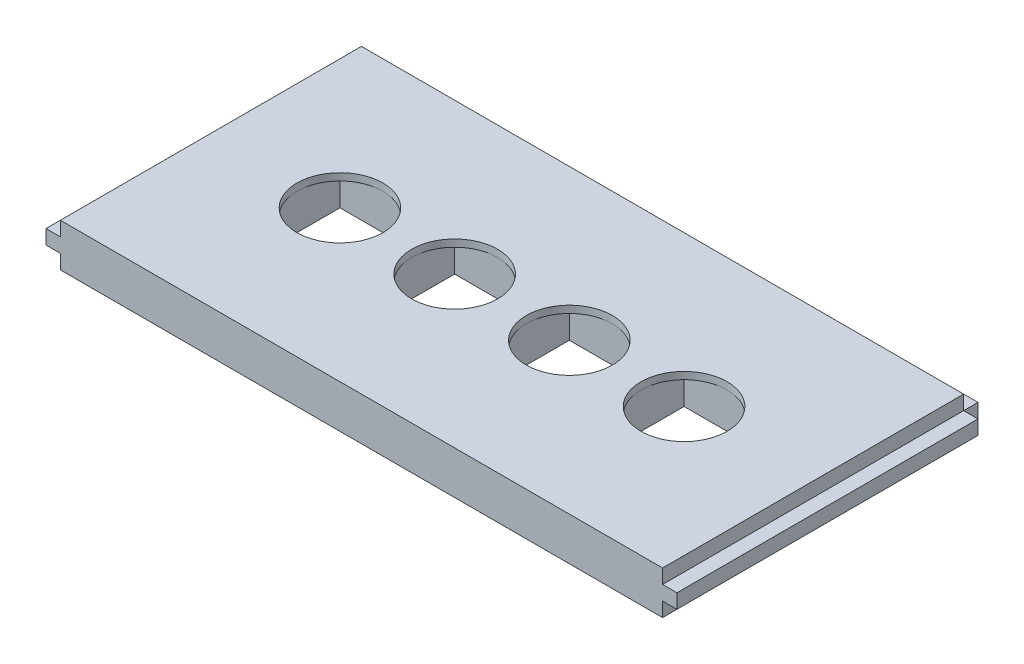
SolidWorks part; units mm, degrees
ref_plane "Спереди" through (0, 0, 0) normal (0, 0, 1) x (1, 0, 0)
ref_plane "Сверху" through (0, 0, 0) normal (0, 1, 0) x (1, 0, 0)
ref_plane "Справа" through (0, 0, 0) normal (1, 0, 0) x (0, 0, -1)
sketch "Эскиз1" plane through (0, 0, 0) normal (0, 1, 0) x (1, 0, 0)
  line L1 (0, 0) -> (42, 0)
  line L2 (0, 0) -> (0, -21)
  line L3 (0, -21) -> (42, -21)
  line L4 (42, 0) -> (42, -21)
  dimension "D1" = 42
  dimension "D2" = 21
extrude "Бобышка-Вытянуть1" add sketch "Эскиз1" along normal blind 3
sketch "Эскиз2" plane through (0, 0, 0) normal (0, -1, 0) x (1, 0, 0)
  line L0 (14, 13.5) -> (20, 13.5)
  line L1 (6, 13.5) -> (12, 13.5)
  line L2 (6, 13.5) -> (6, 7.5)
  line L3 (6, 7.5) -> (12, 7.5)
  line L4 (12, 13.5) -> (12, 7.5)
  line L5 (14, 13.5) -> (14, 7.5)
  line L6 (20, 13.5) -> (20, 7.5)
  line L7 (14, 7.5) -> (20, 7.5)
  line L8 (22, 13.5) -> (28, 13.5)
  line L9 (22, 13.5) -> (22, 7.5)
  line L10 (28, 13.5) -> (28, 7.5)
  line L11 (22, 7.5) -> (28, 7.5)
  line L12 (30, 13.5) -> (36, 13.5)
  line L13 (30, 13.5) -> (30, 7.5)
  line L14 (36, 13.5) -> (36, 7.5)
  line L15 (30, 7.5) -> (36, 7.5)
  line L16 (6, 13.5) -> (14, 13.5) construction
  line L17 (0, 0) -> (0, 21) construction
  line L18 (0, 21) -> (42, 21) construction
  line L19 (9, 10.5) -> (17, 10.5) construction
  circle A0 centre (9, 10.5) radius 3
  circle A1 centre (17, 10.5) radius 3
  circle A2 centre (25, 10.5) radius 3
  circle A3 centre (33, 10.5) radius 3
  dimension "D1" = 6
  dimension "D2" = 6
  dimension "D4" = 8
  dimension "D5" = 6
  dimension "D6" = 7.5
  dimension "D8" = 8
  dimension "D3" = 4
  dimension "D7" = 4
extrude "Вырез-Вытянуть4" cut sketch "Эскиз2" against normal blind 3 contours A0 | A1 | A2 | A3 region at (17, 0, 10.5) region at (9, 0, 10.5) region at (25, 0, 10.5) region at (33, 0, 10.5)
extrude "Вырез-Вытянуть6" cut sketch "Эскиз2<5>" against normal blind 2.5 contours A0 L1 L2 | A0 L2 L3 | A0 L4 L1 | A0 L3 L4 | A1 L0 L5 | A1 L5 L7 | A1 L6 L0 | A1 L7 L6 | A2 L8 L9 | A2 L10 L8 | A2 L9 L11 | A2 L11 L10 | A3 L12 L13 | A3 L13 L15 | A3 L14 L12 | A3 L15 L14 region at (14.6701, 0, 12.8299) region at (19.3299, 0, 12.8299) region at (14.6701, 0, 8.1701) region at (19.3299, 0, 8.1701) region at (6.6701, 0, 12.8299) region at (11.3299, 0, 12.8299) region at (6.6701, 0, 8.1701) region at (11.3299, 0, 8.1701) region at (22.6701, 0, 12.8299) region at (27.3299, 0, 12.8299) region at (22.6701, 0, 8.1701) region at (27.3299, 0, 8.1701) region at (30.6701, 0, 12.8299) region at (35.3299, 0, 12.8299) region at (30.6701, 0, 8.1701) region at (35.3299, 0, 8.1701)
sketch "Эскиз2<5>" plane through (0, 0, 0) normal (0, -1, 0) x (1, 0, 0) same geometry as "Эскиз2"
sketch "Эскиз5" plane through (42, 0, 0) normal (1, 0, 0) x (0, 0, -1)
  line L0 (-21, 3) -> (-21, 0) construction
  line L1 (-21, 2) -> (0, 2)
  line L2 (-21, 2) -> (-21, 1)
  line L3 (-21, 1) -> (0, 1)
  line L4 (0, 2) -> (0, 1)
  line L5 (0, 3) -> (0, 0) construction
  line L6 (-21, 3) -> (0, 3) construction
  point P8 (-21, 1.1006)
  point P9 (-21, 1.8881)
  dimension "D1" = 1
  dimension "D2" = 1
sketch "Эскиз7" plane through (0, 0, 0) normal (0, 0, -1) x (-1, 0, 0)
  line L0 (-42, 2) -> (-42, 1)
  line L1 (-42, 2) -> (0, 2)
  line L2 (-42, 1) -> (0, 1)
  line L3 (0, 2) -> (0, 1)
  line L4 (-42, 2) -> (-42, 1) construction
  line L5 (-42, 2) -> (-42, 1) construction
  line L6 (-42, 3) -> (-42, 0) construction
  line L7 (-42, 3) -> (0, 3) construction
  line L8 (0, 3) -> (0, 0) construction
  point P10 (0, 0)
  point P13 (0, 1)
  dimension "D1" = 1
  dimension "D2" = 1
sketch "Эскиз8" plane through (0, 0, 0) normal (-1, 0, 0) x (0, 0, 1)
  line L1 (0, 2) -> (21, 2)
  line L2 (0, 2) -> (0, 1)
  line L3 (0, 1) -> (21, 1)
  line L4 (21, 2) -> (21, 1)
extrude "Бобышка-Вытянуть2" add sketch "Эскиз5" along normal blind 1
extrude "Бобышка-Вытянуть3" add sketch "Эскиз7" along normal blind 1
extrude "Бобышка-Вытянуть4" add sketch "Эскиз8" along normal blind 1
